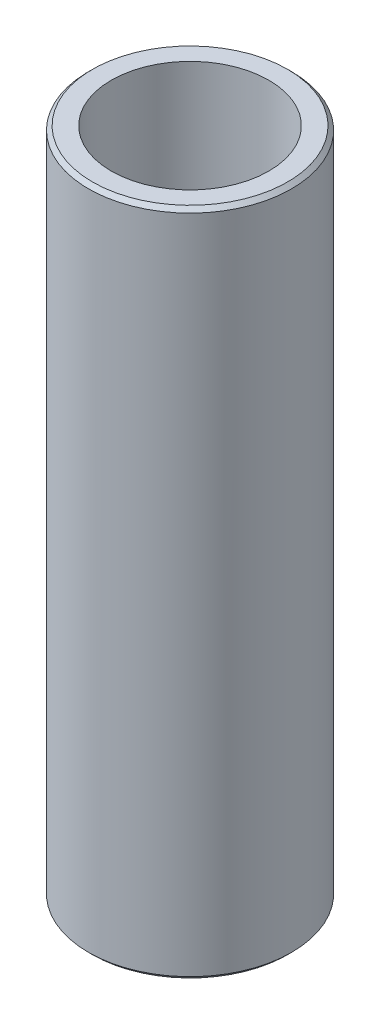
SolidWorks part; units mm, degrees
ref_plane "Front Plane" through (0, 0, 0) normal (0, 0, 1) x (1, 0, 0)
ref_plane "Top Plane" through (0, 0, 0) normal (0, 1, 0) x (1, 0, 0)
ref_plane "Right Plane" through (0, 0, 0) normal (1, 0, 0) x (0, 0, -1)
sketch "Sketch1" plane through (0, 0, 0) normal (0, 1, 0) x (1, 0, 0)
  circle A0 centre (0, 0) radius 57.5
  dimension "SHAFT_OD" = 115
extrude "Boss-Extrude1" add sketch "Sketch1" along normal blind 378.8876
sketch "Sketch2" plane through (0, 0, 0) normal (0, 1, 0) x (1, 0, 0)
  circle A0 centre (0, 0) radius 44.6006
  dimension "BORE_D" = 89.2012
extrude "Cut-Extrude1" cut sketch "Sketch2" along normal through all
chamfer "Chamfer1" distance 2.2517 angle 45 2 edges at (0, 378.8876, 57.5) (0, 0, 57.5)
